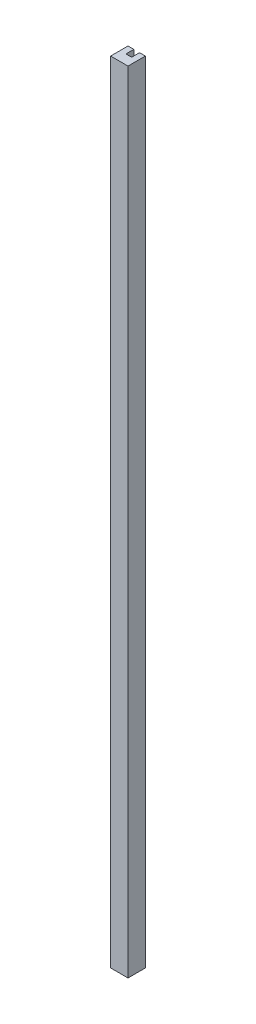
SolidWorks part; units mm, degrees
material "Oak"
ref_plane "Front Plane" through (0, 0, 0) normal (0, 0, 1) x (1, 0, 0)
ref_plane "Top Plane" through (0, 0, 0) normal (0, 1, 0) x (1, 0, 0)
ref_plane "Right Plane" through (0, 0, 0) normal (1, 0, 0) x (0, 0, -1)
other "Configuration Table"
sketch "Sketch1" plane through (0, 0, 0) normal (0, 1, 0) x (1, 0, 0)
  line L1 (-27.5, -27.5) -> (27.5, -27.5)
  line L2 (-27.5, -27.5) -> (-27.5, 27.5)
  line L3 (-27.5, 27.5) -> (27.5, 27.5)
  line L4 (27.5, -27.5) -> (27.5, 27.5)
  line L5 (-27.5, -27.5) -> (27.5, 27.5) construction
  line L6 (-27.5, 27.5) -> (27.5, -27.5) construction
  point P0 (0, 0)
  dimension "D1" = 55
extrude "Boss-Extrude1" add sketch "Sketch1" along normal blind 2500
sketch "Sketch2" plane through (0, 0, -27.5) normal (0, 0, -1) x (-1, 0, 0)
  line L0 (9, 0) -> (-27.5, 0) construction
  line L1 (-9, 0) -> (9, 0)
  line L2 (-9, 0) -> (-9, 2500)
  line L3 (-9, 2500) -> (9, 2500)
  line L4 (9, 0) -> (9, 2500)
  line L5 (-27.5, 2500) -> (-27.5, 0) construction
  line L6 (-9, 0) -> (27.5, 0) construction
  line L7 (27.5, 2500) -> (27.5, 0) construction
  line L8 (27.5, 2500) -> (-1972.5, 2500) construction
  line L9 (-27.5, 0) -> (27.5, 0) construction
  dimension "D1" = 18
extrude "Cut-Extrude1" cut sketch "Sketch2" against normal blind 25
